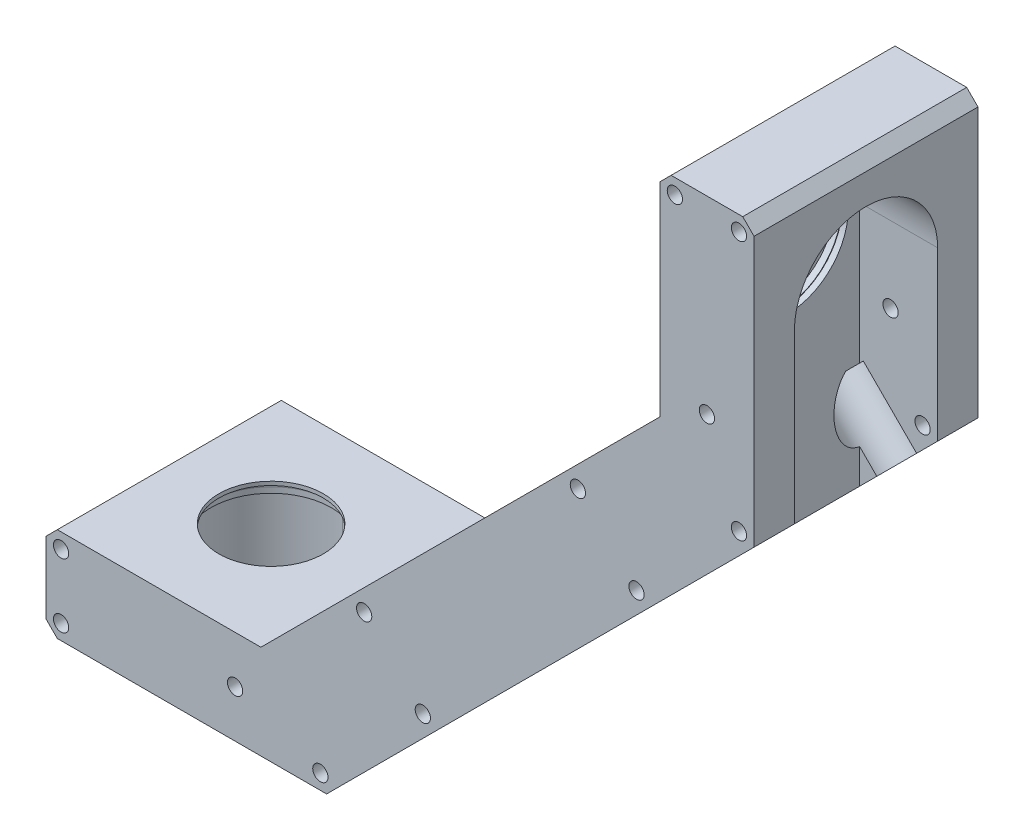
SolidWorks part; units mm, degrees
ref_plane "Front Plane" through (0, 0, 0) normal (0, 0, 1) x (1, 0, 0)
ref_plane "Top Plane" through (0, 0, 0) normal (0, 1, 0) x (1, 0, 0)
ref_plane "Right Plane" through (0, 0, 0) normal (1, 0, 0) x (0, 0, -1)
ref_plane "Plane4" through (0, 0, 0) normal (-0.7071, 0.7071, 0) x (0.7071, 0.7071, 0)
ref_plane "Plane5" through (0, 0, 0) normal (0.7071, 0.7071, 0) x (0.7071, -0.7071, 0)
sketch "Sketch6" plane through (0, 0, 0) normal (0, 0, 1) x (1, 0, 0)
  line L0 (0, 0) -> (0, -132.8) construction
  line L1 (42.7696, -153.8) -> (42.7696, -157.8) construction
  line L2 (-27, -132.8) -> (27, -132.8)
  line L3 (27, -132.8) -> (79.9, -79.9)
  line L4 (38.8909, 38.8909) -> (-38.8909, -38.8909) construction
  line L5 (42.7696, -153.8) -> (-26, -153.8) construction
  line L6 (150.3808, -150.3808) -> (65.864, -65.864) construction
  line L7 (38.8909, -38.8909) -> (-38.8909, 38.8909) construction
  line L8 (-27, -132.8) -> (-30, -135.8)
  line L10 (44.4264, -157.8) -> (101.1132, -101.1132)
  line L11 (101.1132, -101.1132) -> (79.9, -79.9)
  line L12 (-30, -135.8) -> (-30, -154.8)
  line L13 (-27, -157.8) -> (44.4264, -157.8)
  line L14 (0, -55) -> (0, 55) construction
  line L15 (-26, -153.8) -> (-26, -136.8) construction
  line L16 (-30, -154.8) -> (-27, -157.8)
  line L17 (-30, -154.8) -> (-30, -157.8) construction
  line L18 (-30, -157.8) -> (-27, -157.8) construction
  line L19 (-56.8042, -145.3) -> (-77.2113, -145.3) construction
  line L20 (54.385, -111.0718) -> (51.5566, -108.2434) construction
  line L23 (69.9414, -126.6282) -> (72.7698, -129.4566) construction
  line L24 (42.7696, -153.8) -> (45.598, -156.6284) construction
  line L25 (27, -132.8) -> (20.1569, -132.8) construction
  line L26 (20.1569, -132.8) -> (20.1569, -145.3) construction
  line L27 (27, -132.8) -> (17.3284, -142.4716) construction
  line L28 (17.3284, -142.4716) -> (20.1569, -145.3) construction
  line L29 (-26, -153.8) -> (-30, -153.8) construction
  line L30 (-26, -153.8) -> (-26, -157.8) construction
  circle A0 centre (-26, -153.8) radius 2.025
  circle A1 centre (42.7696, -153.8) radius 2.025
  circle A2 centre (-26, -136.8) radius 2.025
  circle A3 centre (20.1569, -145.3) radius 2.025
  circle A4 centre (69.9414, -126.6282) radius 2.025
  circle A6 centre (54.385, -111.0718) radius 2.025
  point P27 (-30, -145.3)
  dimension "D7" = 4.05
  dimension "D1" = 132.8
  dimension "D2" = 54
  dimension "D3" = 45
  dimension "D4" = 25
  dimension "D5" = 3
  dimension "D6" = 30
  dimension "D8" = 4
extrude "Boss-Extrude4" add sketch "Sketch6" along normal blind 29.7 and the other way blind 29.7
sketch "Sketch7" plane through (0, 0, 0) normal (0, 0, 1) x (1, 0, 0)
  line L0 (-13.85, -133.8) -> (-13.85, -132.8)
  line L1 (-15.85, -133.8) -> (-13.85, -133.8)
  line L2 (-15.85, -133.8) -> (-15.85, -135.492)
  line L3 (-15.85, -135.492) -> (-16, -135.492)
  line L4 (-16, -135.492) -> (-16, -137.092)
  line L5 (-16, -137.092) -> (-19, -137.092)
  line L6 (-19, -137.092) -> (-19, -157.8)
  line L7 (-19, -157.8) -> (0, -157.8)
  line L8 (0, -157.8) -> (0, -132.8)
  line L9 (-13.85, -132.8) -> (0, -132.8)
  line L10 (0, 0) -> (0, -132.8) construction
  line L11 (-27, -157.8) -> (44.4264, -157.8) construction
  line L12 (0, -176.4489) -> (0, -119.3367) construction
  line L13 (-27, -132.8) -> (27, -132.8) construction
  point P20 (-6.925, -132.8)
  dimension "D1" = 32
  dimension "D2" = 3
  dimension "D3" = 1.6
  dimension "D4" = 0.15
  dimension "D5" = 2.692
  dimension "D6" = 1
  dimension "D7" = 2
revolve "Cut-Revolve1" cut sketch "Sketch7" angle 360 about L12
sketch "Sketch8" plane through (0, -137.092, 0) normal (0, -1, 0) x (1, 0, 0)
  line L0 (0, -19) -> (100, -19)
  line L2 (100, -19) -> (100, 19)
  line L3 (100, 0) -> (35.5744, 0) construction
  line L4 (0, -19) -> (0, 0)
  line L5 (0, 19) -> (100, 19)
  arc A0 (0, -19) -> (0, 19) centre (0, 0) ccw
  circle A1 centre (0, 0) radius 19 construction
  circle M5 centre (0, 0) radius 19
  dimension "D1" = 100
extrude "Cut-Extrude1" cut sketch "Sketch8" along normal through all contours L5 L0 L2 M5 region at (57.3556, -137.092, 0)
mirror "Mirror1" about plane through (0, 0, 0) normal (0.7071, 0.7071, 0) of "Cut-Extrude1", "Cut-Revolve1", "Boss-Extrude4"
sketch "Sketch10" plane through (79.9, -79.9, 0) normal (-0.7071, 0.7071, 0) x (0, 0, 1)
  line L0 (-19.7, -64.8119) -> (19.7, -64.8119) construction
  line L1 (19.7, -64.8119) -> (19.7, 64.8119) construction
  line L2 (19.7, 64.8119) -> (-19.7, 64.8119) construction
  line L3 (-19.7, 64.8119) -> (-19.7, -64.8119) construction
  line L4 (-48.9099, 0) -> (-32.8882, 0) construction
  line L5 (0, -3.8242) -> (0, 19.0187) construction
  line L6 (55, 0) -> (-55, 0) construction
  line L7 (0, -119.2795) -> (0, 119.2795) construction
  line L8 (-19.7, -64.8119) -> (-29.7, -64.8119) construction
  line L9 (-19.7, -64.8119) -> (-19.7, -74.8119) construction
  line L10 (-29.7, -74.8119) -> (29.7, -74.8119) construction
  line L11 (-29.7, 74.8119) -> (-29.7, -74.8119) construction
  circle A0 centre (-19.7, -64.8119) radius 2
  circle A1 centre (19.7, -64.8119) radius 2
  circle A2 centre (-19.7, 64.8119) radius 2
  circle A3 centre (19.7, 64.8119) radius 2
  point P14 (-14.7, -64.1608)
  point P17 (-24.7, -60.1825)
  dimension "D1" = 4
  dimension "D2" = 10
  dimension "D3" = 10
extrude "Cut-Extrude2" cut sketch "Sketch10" against normal through all
sketch "Sketch11" plane through (101.1132, -101.1132, 0) normal (0.7071, -0.7071, 0) x (0, 0, -1)
  circle A0 centre (19.7, -64.8119) radius 7.5
  circle A1 centre (-19.7, -64.8119) radius 7.5
  circle A2 centre (-19.7, 64.8119) radius 7.5
  circle A3 centre (19.7, 64.8119) radius 7.5
  dimension "D1" = 15
extrude "Cut-Extrude3" cut sketch "Sketch11" against normal blind 20
equation "\"EyeDiameter\" = 100"
equation "\"L2Thickness\" = 15"
equation "\"EyeClearance\" = 2"
equation "\"BasePlaneDistance\" = \"EyeDiameter\"/2+\"L2Thickness\"+\"EyeClearance\""
equation "\"L2_ID\" = 20"
equation "\"vx\" = 0"
equation "\"vy\" = 0"
equation "\"vz\" = 100"
equation "\"parametric_end\" = 1"
equation "\"Rw_3_xx\" = -(\"vz\")/sqr((\"vx\")^2 + (\"vz\")^2)"
equation "\"Rw_3_xy\" = 0"
equation "\"Rw_3_xz\" = (\"vx\")/sqr((\"vx\")^2 + (\"vz\")^2)"
equation "\"Rw_3_zx\" = (\"vx\")/sqr((\"vx\")^2 + (\"vy\")^2 + (\"vz\")^2)"
equation "\"Rw_3_zy\" = (\"vy\")/sqr((\"vx\")^2 + (\"vy\")^2 + (\"vz\")^2)"
equation "\"Rw_3_zz\" = (\"vz\")/sqr((\"vx\")^2 + (\"vy\")^2 + (\"vz\")^2)"
equation "\"Rw_3_yx\" = (\"vx\")*(\"vy\")/sqr((\"vx\")^4 + (\"vx\")^2*(\"vy\")^2 + 2*(\"vx\")^2*(\"vz\")^2 + (\"vy\")^2*(\"vz\")^2 + (\"vz\")^4)"
equation "\"Rw_3_yy\" = -sqr((\"vx\")^2 + (\"vz\")^2)/sqr((\"vx\")^2 + (\"vy\")^2 + (\"vz\")^2)"
equation "\"Rw_3_yz\" = (\"vy\")*(\"vz\")/sqr((\"vx\")^4 + (\"vx\")^2*(\"vy\")^2 + 2*(\"vx\")^2*(\"vz\")^2 + (\"vy\")^2*(\"vz\")^2 + (\"vz\")^4)"
equation "\"O2Targx\" = -\"BasePlaneDistance\"*(\"vx\")*(\"vy\")/sqr((\"vx\")^4 + (\"vx\")^2*(\"vy\")^2 + 2*(\"vx\")^2*(\"vz\")^2 + (\"vy\")^2*(\"vz\")^2 + (\"vz\")^4)"
equation "\"O2Targy\" = \"BasePlaneDistance\"*sqr((\"vx\")^2 + (\"vz\")^2)/sqr((\"vx\")^2 + (\"vy\")^2 + (\"vz\")^2)"
equation "\"O2Targz\" = -\"BasePlaneDistance\"*(\"vy\")*(\"vz\")/sqr((\"vx\")^4 + (\"vx\")^2*(\"vy\")^2 + 2*(\"vx\")^2*(\"vz\")^2 + (\"vy\")^2*(\"vz\")^2 + (\"vz\")^4)"
equation "\"O2Targx_0\" = -(\"BasePlaneDistance\")*sqr((\"vx\")^2 + (\"vz\")^2)/sqr((\"vx\")^2 + (\"vy\")^2 + (\"vz\")^2)"
equation "\"O2Targy_0\" = -(\"BasePlaneDistance\")*(\"vy\")*(\"vz\")/sqr((\"vx\")^4 + (\"vx\")^2*(\"vy\")^2 + 2*(\"vx\")^2*(\"vz\")^2 + (\"vy\")^2*(\"vz\")^2 + (\"vz\")^4)"
equation "\"O2Targz_0\" = (\"BasePlaneDistance\")*(\"vx\")*(\"vy\")/sqr((\"vx\")^4 + (\"vx\")^2*(\"vy\")^2 + 2*(\"vx\")^2*(\"vz\")^2 + (\"vy\")^2*(\"vz\")^2 + (\"vz\")^4) + (\"BasePlaneDistance\")"
equation "\"theta2_s1\" = arcsin(((\"BasePlaneDistance\") - (\"O2Targz_0\"))/(\"BasePlaneDistance\")) + pi"
equation "\"theta2_s2\" = -arcsin(((\"BasePlaneDistance\") - (\"O2Targz_0\"))/(\"BasePlaneDistance\"))"
equation "\"Theta2\" = \"theta2_s2\""
equation "\"theta1_s1\" = arcsin((\"O2Targy_0\")/((\"BasePlaneDistance\")*cos((\"Theta2\")))) + pi"
equation "\"theta1_s2\" = -arcsin((\"O2Targy_0\")/((\"BasePlaneDistance\")*cos((\"Theta2\"))))"
equation "\"theta1_s3\" = -arccos(-(\"O2Targx_0\")/((\"BasePlaneDistance\")*cos((\"Theta2\")))) + 2*pi"
equation "\"theta1_s4\" = arccos(-(\"O2Targx_0\")/((\"BasePlaneDistance\")*cos((\"Theta2\"))))"
equation "\"Theta1\" = \"theta1_s2\" 'so far, theta1_s1 and theta1_s4 have agreed, and they agree with the sw constraint solver"
equation "\"o2_x\" = -(\"BasePlaneDistance\")*cos((\"Theta1\"))*cos((\"Theta2\"))"
equation "\"o2_y\" = -(\"BasePlaneDistance\")*sin((\"Theta1\"))*cos((\"Theta2\"))"
equation "\"o2_z\" = (\"BasePlaneDistance\")*(sin((\"Theta2\")) + 1)"
equation "\"o1_x\" = (\"BasePlaneDistance\")*sin((\"Theta1\"))"
equation "\"o1_y\" = -(\"BasePlaneDistance\")*cos((\"Theta1\"))"
equation "\"o1_z\" = (\"BasePlaneDistance\")"
equation "\"Actuator1_Theta\" = atn(\"vx\"/\"vz\")\t'ik solution for the single link joint"
equation "\"Actuator2_Theta\" = \"Theta1\"\t\t'ik solution for the double link joint"
equation "\"MotorBaseThickness\" = 25\t"
equation "\"BaseThickness\" = 30\t\t"
equation "\"pcb_thickness\" = 1.6\t\t'Thickness of the PCB"
equation "\"EncoderToMagnetAirgap\" = 1\t'Encoder to magnet airgap"
equation "\"EncoderHeight\" = 1.192\t\t'Height of the encoder"
equation "\"MagnetThickness\" = 0.5\t\t'Magnet thickness"
equation "\"pcb_outer_diameter\" = 32\t'the OD of the pcb"
equation "\"D1@Sketch6\" = \"BasePlaneDistance\" + \"OverallLength@BigMotorStator<1>.Part\""
equation "\"D2@Sketch6\" = \"StatorBaseOD@BigMotorStator<1>.Part\""
equation "\"D4@Sketch6\"= \"MotorBaseThickness\""
equation "\"D6@Sketch6\"= \"BaseThickness\""
equation "\"D1@Boss-Extrude4\" = \"StatorBaseOD@BigMotorStator<1>.Part\" * 0.55"
equation "\"D2@Boss-Extrude4\" = \"StatorBaseOD@BigMotorStator<1>.Part\" * 0.55"
equation "\"D5@Sketch7\"=\"EncoderHeight\"+\"EncoderToMagnetAirgap\"+\"MagnetThickness\""
equation "\"D3@Sketch7\"=\"pcb_thickness\""
equation "\"D1@Sketch7\"=\"pcb_outer_diameter\""
